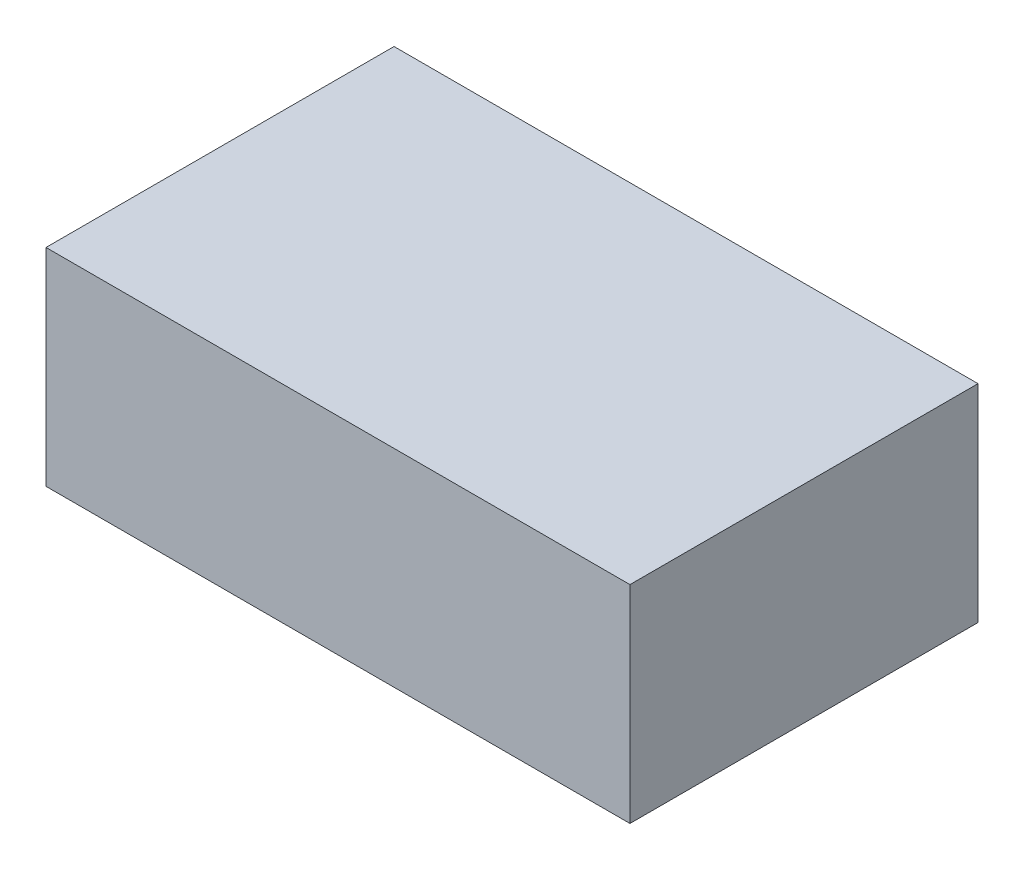
SolidWorks part; units mm, degrees
ref_plane "Спереди" through (0, 0, 0) normal (0, 0, 1) x (1, 0, 0)
ref_plane "Сверху" through (0, 0, 0) normal (0, 1, 0) x (1, 0, 0)
ref_plane "Справа" through (0, 0, 0) normal (1, 0, 0) x (0, 0, -1)
sketch "Эскиз1" plane through (0, 0, 0) normal (0, 1, 0) x (1, 0, 0)
  line L1 (-75.5, 45) -> (75.5, 45)
  line L2 (-75.5, 45) -> (-75.5, -45)
  line L3 (-75.5, -45) -> (75.5, -45)
  line L4 (75.5, 45) -> (75.5, -45)
  line L5 (-75.5, 45) -> (75.5, -45) construction
  line L6 (-75.5, -45) -> (75.5, 45) construction
  point P0 (0, 0)
  dimension "D1" = 90
  dimension "D2" = 151
extrude "Бобышка-Вытянуть1" add sketch "Эскиз1" along normal blind 53.5
sketch "Эскиз2" plane through (75.5, 0, 0) normal (1, 0, 0) x (0, 0, -1)
  line L3 (-44, 53.5) -> (44, 53.5)
  line L5 (-45, 53.5) -> (45, 53.5) construction
  line L7 (-44, 53.5) -> (-45, 0)
  line L8 (44, 53.5) -> (45, 0)
  line L9 (-45, 0) -> (45, 0) construction
  line L12 (-45, 0) -> (45, 0)
  line L13 (45, 0) -> (45, 53.5)
  line L14 (45, 53.5) -> (-45, 53.5)
  line L15 (-45, 53.5) -> (-45, 0)
  line L16 (-45, 0) -> (45, 0)
  point P8 (0, 0)
  point P9 (0, 0)
  dimension "D1" = 88
  dimension "D2" = 0
sketch "Эскиз3" plane through (0, 0, 45) normal (0, 0, 1) x (1, 0, 0)
  line L0 (-75.5, 0) -> (-74.5, 53.5)
  line L1 (-74.5, 53.5) -> (74.5, 53.5)
  line L2 (74.5, 53.5) -> (75.5, 0)
  line L3 (-75.5, 53.5) -> (75.5, 53.5) construction
  line L8 (-75.5, 0) -> (75.5, 0)
  line L9 (75.5, 0) -> (75.5, 53.5)
  line L10 (75.5, 53.5) -> (-75.5, 53.5)
  line L11 (-75.5, 53.5) -> (-75.5, 0)
  line L12 (-75.5, 0) -> (75.5, 0)
  dimension "D1" = 149
  dimension "D2" = 0
extrude "Бобышка-Вытянуть3" add sketch "Эскиз2" against normal up to surface (151 mm away) separate body up to face at (-75.5, 26.75, 0)
extrude "Бобышка-Вытянуть4" add sketch "Эскиз3" against normal up to surface (90 mm away) separate body up to face at (0, 26.75, -45)
combine bodies "Соединить1" operation type common bodies to combine 106 105
fillet "Скругление1" radius 5 4 edges at (75, 26.75, -44.5) (75, 26.75, 44.5) (-75, 26.75, 44.5) (-75, 26.75, -44.5)
fillet "Скругление2" radius 5 8 edges at (-73.0359, 53.5, -42.5359) (-74.5, 53.5, 0) (-73.0359, 53.5, 42.5359) (0, 53.5, 44) (73.0359, 53.5, 42.5359) (74.5, 53.5, 0) (73.0359, 53.5, -42.5359) (0, 53.5, -44)
fillet "Скругление3" radius 2 8 edges at (-74.0359, 0, 43.5359) (-75.5, 0, 0) (-74.0359, 0, -43.5359) (0, 0, -45) (74.0359, 0, -43.5359) (75.5, 0, 0) (74.0359, 0, 43.5359) (0, 0, 45)
